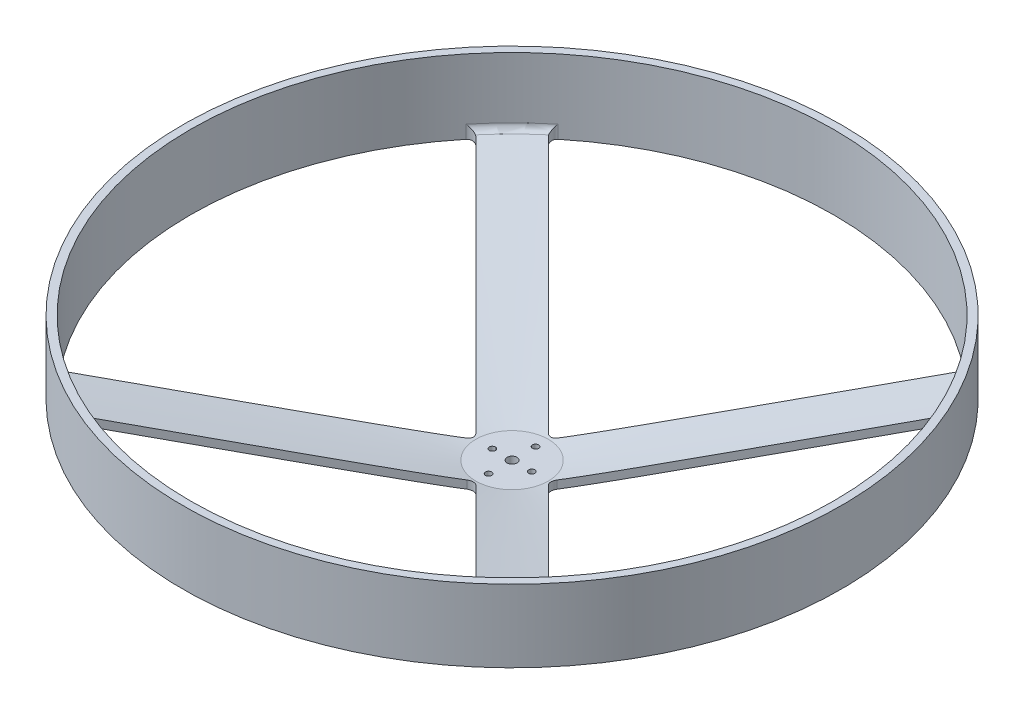
SolidWorks part; units mm, degrees
ref_plane "Front Plane" through (0, 0, 0) normal (0, 0, 1) x (1, 0, 0)
ref_plane "Top Plane" through (0, 0, 0) normal (0, 1, 0) x (1, 0, 0)
ref_plane "Right Plane" through (0, 0, 0) normal (1, 0, 0) x (0, 0, -1)
sketch "Sketch1" plane through (0, 0, 0) normal (0, 0, 1) x (1, 0, 0)
  line L0 (0, 0) -> (133.35, 0)
  line L1 (133.35, 0) -> (133.35, -29.2878)
  line L2 (133.35, -29.2878) -> (14.986, -53.975)
  line L3 (14.986, -53.975) -> (0, -53.975)
  line L4 (0, -53.975) -> (0, 0)
  point P3 (0, 0)
  point P7 (17.9158, -54.1691)
  point P8 (0, 0)
  point P9 (0, 0)
revolve "Revolve1" add sketch "Sketch1" angle 360 about L4
shell "Shell1" thickness 3.175 removed face at (0, 0, -133.35)
ref_plane "Plane1" through (0, -53.975, 0) normal (0, 1, 0) x (1, 0, 0)
sketch "Sketch2" plane through (0, 0, 0) normal (0, 1, 0) x (1, 0, 0)
  line L4 (-14.6584, 0) -> (-99.0846, -84.4262)
  line L5 (0, -14.6584) -> (-84.4262, -99.0846)
  line L6 (-29.6862, 0) -> (29.6862, 0) construction
  line L7 (0, 14.6584) -> (-84.4262, 99.0846)
  line L8 (-14.6584, 0) -> (-99.0846, 84.4262)
  line L9 (0, -29.6862) -> (0, 29.6862) construction
  line L10 (0, 14.6584) -> (84.4262, 99.0846)
  line L11 (14.6584, 0) -> (99.0846, 84.4262)
  line L12 (0, -14.6584) -> (84.4262, -99.0846)
  line L13 (14.6584, 0) -> (99.0846, -84.4262)
  circle A0 centre (0, 0) radius 130.175
  circle A1 centre (0, 0) radius 14.6584
extrude "Cut-Extrude1" cut sketch "Sketch2" against normal through all contours L5 A0 L12 | L8 A0 L4 | L10 A0 L7 | L13 A0 L11 region at (-84.5878, 0, 0) region at (0, 0, -84.5878) region at (0, 0, 84.5878) region at (84.5878, 0, 0)
fillet "Fillet1" radius 2.54 4 edges at (-14.6584, -52.3875, 0) (0, -52.3875, 14.6584) (0, -52.3875, -14.6584) (14.6584, -52.3875, 0)
fillet "Fillet2" radius 2.54 12 edges at (-84.4262, -28.3283, 99.0846) (-92.0476, -26.7067, 92.0476) (-99.0846, -28.3283, 84.4262) (84.4262, -28.3283, 99.0846) (92.0476, -26.7067, 92.0476) (99.0846, -28.3283, 84.4262) (-84.4262, -28.3283, -99.0846) (-99.0846, -28.3283, -84.4262) (-92.0476, -26.7067, -92.0476) (99.0846, -28.3283, -84.4262) (92.0476, -26.7067, -92.0476) (84.4262, -28.3283, -99.0846)
sketch "Sketch3" plane through (0, -50.8, 0) normal (0, 1, 0) x (1, 0, 0)
  circle A0 centre (0, 0) radius 2
  circle A1 centre (0, -9.5) radius 1.25
  circle A2 centre (8, 0) radius 1.25
  circle A3 centre (0, 9.5) radius 1.25
  circle A4 centre (-8, 0) radius 1.25
  dimension "D1" = 9.5
  dimension "D2" = 9.5
  dimension "D3" = 8
  dimension "D4" = 8
extrude "Cut-Extrude3" cut sketch "Sketch3" against normal through all
